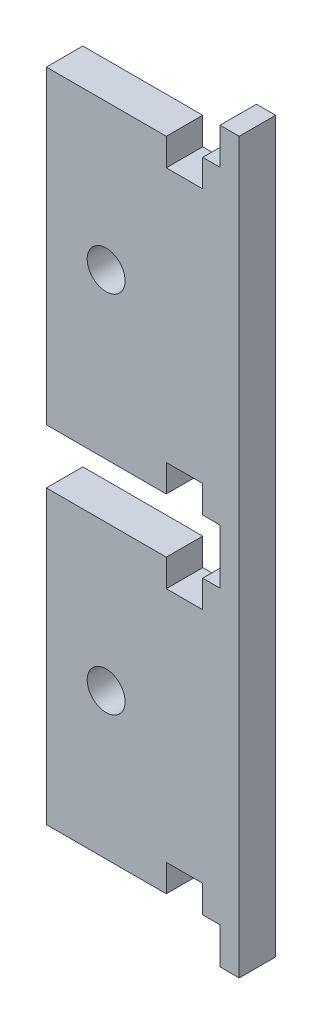
SolidWorks part; units mm, degrees
material "AISI 4130 Steel, annealed at 865C"
ref_plane "X-Y Datum" through (0, 0, 0) normal (0, 0, 1) x (1, 0, 0)
ref_plane "X-Z Datum" through (0, 0, 0) normal (0, 1, 0) x (1, 0, 0)
ref_plane "Y-Z Datum" through (0, 0, 0) normal (1, 0, 0) x (0, 0, -1)
sketch "Sketch2" plane through (0, 0, 0) normal (0, 0, 1) x (1, 0, 0)
  line L0 (34.925, 127) -> (0, 127) construction
  line L1 (0, 0) -> (40.64, 0)
  line L2 (0, 0) -> (0, 127)
  line L3 (0, 127) -> (40.64, 127)
  line L4 (40.64, 0) -> (40.64, 127)
  point P7 (17.4625, 31.75)
  point P8 (17.4625, 95.25)
  dimension "D1" = 40.64
extrude "Boss-Extrude1" add sketch "Sketch2" along normal blind 6.35
hole_wizard "M6 Clearance Hole1" positions "Sketch3" profile "Sketch4" hole size "M6" standard "ANSI Metric" end condition through all
sketch "Sketch3" plane through (0, 0, 6.35) normal (0, 0, 1) x (1, 0, 0)
  point P0 (17.4625, 31.75)
  point P3 (17.4625, 95.25)
sketch "Sketch4" plane through (17.4625, 31.75, 6.35) normal (1, 0, 0) x (0, -1, 0)
  line L0 (0, 0) -> (0, 6.35)
  line L1 (0, 6.35) -> (3.3, 6.35)
  line L2 (3.3, 6.35) -> (3.3, 0)
  line L5 (3.3, 0) -> (0, 0)
  line L11 (0, -6.35) -> (0, 107.95) construction
  dimension "Thru Hole Dia." = 6.6
  dimension "Thru Hole Depth" = 6.35
sketch "Sketch5" plane through (0, 0, 6.35) normal (0, 0, 1) x (1, 0, 0)
  line L0 (7.0505, 127) -> (7.0505, 0)
  line L1 (40.64, 127) -> (0, 127) construction
  line L2 (0, 0) -> (40.64, 0) construction
  circle A0 centre (17.4625, 95.25) radius 3.3 construction
  point P6 (14.1625, 95.25)
  line M4 (0, 127) -> (0, 0)
  line M5 (0, 0) -> (40.64, 0)
  line M7 (40.64, 127) -> (0, 127)
  dimension "D1" = 7.112
extrude "Cut-Extrude1" cut sketch "Sketch5" against normal through all and the other way through all contours L0 M7 M4 M5 region at (3.5252, 63.5, 6.35)
sketch "Sketch6" plane through (0, 0, 6.35) normal (0, 0, 1) x (1, 0, 0)
  line L0 (-3.175, 120.65) -> (38.1, 120.65)
  line L1 (38.1, 120.65) -> (38.1, 130.175)
  line L2 (38.1, 130.175) -> (-3.175, 130.175)
  line L3 (-3.175, 130.175) -> (-3.175, 120.65)
  line L4 (0, 123.825) -> (34.925, 123.825)
  line L5 (34.925, 123.825) -> (34.925, 127)
  line L6 (34.925, 127) -> (0, 127)
  line L7 (0, 127) -> (0, 123.825)
  line L8 (0, 123.825) -> (34.925, 123.825)
  line L9 (34.925, 123.825) -> (34.925, 127)
  line L10 (34.925, 127) -> (0, 127)
  line L11 (0, 127) -> (0, 123.825)
  line L12 (0, 60.325) -> (34.925, 60.325)
  line L13 (34.925, 60.325) -> (34.925, 63.5)
  line L14 (34.925, 63.5) -> (0, 63.5)
  line L15 (0, 63.5) -> (0, 60.325)
  line L16 (0, 60.325) -> (34.925, 60.325)
  line L17 (34.925, 60.325) -> (34.925, 63.5)
  line L18 (34.925, 63.5) -> (0, 63.5)
  line L19 (0, 63.5) -> (0, 60.325)
  line L24 (0, 0) -> (34.925, 0)
  line L25 (34.925, 0) -> (34.925, 3.175)
  line L26 (34.925, 3.175) -> (0, 3.175)
  line L27 (0, 3.175) -> (0, 0)
  line L28 (38.1, 66.675) -> (-3.175, 66.675)
  line L29 (-3.175, 66.675) -> (-3.175, 57.15)
  line L30 (-3.175, 57.15) -> (38.1, 57.15)
  line L31 (38.1, 57.15) -> (38.1, 66.675)
  line L32 (38.1, 6.35) -> (-3.175, 6.35)
  line L33 (-3.175, 6.35) -> (-3.175, -3.175)
  line L34 (-3.175, -3.175) -> (38.1, -3.175)
  line L35 (38.1, -3.175) -> (38.1, 6.35)
  line L36 (37.3063, 127) -> (37.3063, 0)
  line L37 (40.64, 127) -> (7.0505, 127) construction
  line L38 (7.0505, 0) -> (40.64, 0) construction
  line M19 (7.0505, 127) -> (7.0505, 0)
  line M20 (7.0505, 0) -> (40.64, 0)
  line M22 (40.64, 127) -> (7.0505, 127)
  dimension "D5" = 2.3813
  dimension "D1" = 0
  dimension "D2" = 0
  dimension "D4" = 3.175
extrude "Cut-Extrude2" cut sketch "Sketch6" against normal through all contours L36 L9 L8 L0 M22 M19 | L8 L9 M22 M19 | L36 L28 L18 L17 L16 L30 M19 | L17 L18 L16 M19 | L36 L32 L26 L25 M19 M20 | L25 L26 M19 M20 region at (23.1953, 122.4692, 6.35) region at (20.9877, 125.4125, 6.35) region at (22.1784, 66.3578, 6.35) region at (20.9878, 61.9125, 6.35) region at (23.1953, 4.5308, 6.35) region at (20.9878, 1.5875, 6.35)
sketch "Sketch7" plane through (0, 0, 6.35) normal (0, 0, 1) x (1, 0, 0)
  line L18 (34.29, 120.65) -> (27.94, 120.65)
  line L19 (34.29, 120.65) -> (34.29, 115.8875)
  line L20 (34.29, 115.8875) -> (27.94, 115.8875)
  line L21 (27.94, 120.65) -> (27.94, 115.8875)
  line L22 (34.29, 71.4375) -> (27.94, 71.4375)
  line L23 (34.29, 71.4375) -> (34.29, 66.675)
  line L24 (34.29, 66.675) -> (27.94, 66.675)
  line L25 (27.94, 71.4375) -> (27.94, 66.675)
  line L26 (34.29, 57.15) -> (27.94, 57.15)
  line L27 (34.29, 57.15) -> (34.29, 52.3875)
  line L28 (34.29, 52.3875) -> (27.94, 52.3875)
  line L29 (27.94, 57.15) -> (27.94, 52.3875)
  line L30 (34.29, 11.1125) -> (27.94, 11.1125)
  line L31 (34.29, 11.1125) -> (34.29, 6.35)
  line L32 (34.29, 6.35) -> (27.94, 6.35)
  line L33 (27.94, 11.1125) -> (27.94, 6.35)
extrude "Cut-Extrude3" cut sketch "Sketch7" against normal through all
